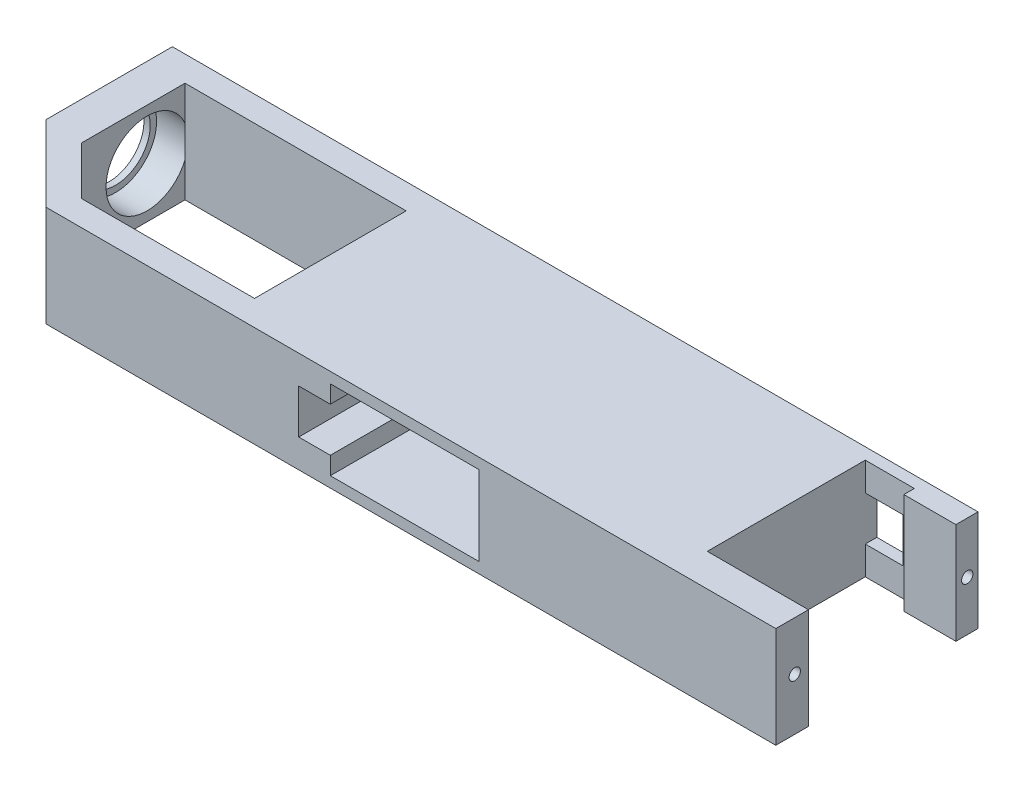
SolidWorks part; units mm, degrees
ref_plane "Front Plane" through (0, 0, 0) normal (0, 0, 1) x (1, 0, 0)
ref_plane "Top Plane" through (0, 0, 0) normal (0, 1, 0) x (1, 0, 0)
ref_plane "Right Plane" through (0, 0, 0) normal (1, 0, 0) x (0, 0, -1)
ref_axis "Axis1" through (0, 0, -88.99) along (0, 0, 1)
ref_axis "Axis2" through (88.99, 0, 0) along (-1, 0, 0)
sketch "Sketch1" plane through (0, 0, 0) normal (0, 1, 0) x (1, 0, 0)
  line L0 (64, -16.836) -> (47.9935, -16.836)
  line L1 (-63.5, 10) -> (64, 10)
  line L2 (-63.5, 10) -> (-63.5, -10)
  line L3 (-51.5, -22) -> (64, -22)
  line L4 (64, 10) -> (64, 6.5)
  line L5 (47.9935, -16.836) -> (47.9935, 8.164)
  line L6 (-63.5, -10) -> (-51.5, -22)
  line L8 (47.9935, 8.164) -> (55.7639, 8.164)
  line L9 (55.7639, 8.164) -> (55.7639, 6.5)
  line L10 (55.7639, 6.5) -> (64, 6.5)
  line L11 (64, -16.836) -> (64, -22)
  point P2 (-63.5, 0)
  dimension "D1" = 127.5
  dimension "D2" = 32
  dimension "D3" = 20
  dimension "D4" = 63.5
  dimension "D5" = 45
  dimension "D6" = 5.164
  dimension "D7" = 16.0065
  dimension "D8" = 25
  dimension "D9" = 3.5
  dimension "D10" = 8.2361
extrude "Boss-Extrude1" add sketch "Sketch1" along normal blind 8 and the other way blind 8
sketch "Sketch2" plane through (-63.5, 0, 0) normal (-1, 0, 0) x (0, 0, 1)
  circle A0 centre (0, 0) radius 5.5
  dimension "D1" = 11
extrude "Cut-Extrude1" cut sketch "Sketch2" against normal blind 8
sketch "Sketch3" plane through (0, 8, 0) normal (0, 1, 0) x (1, 0, 0)
  line L7 (-57.5, 6) -> (-22.5, 6)
  line L8 (-22.5, 6) -> (-22.5, -18)
  line L9 (-22.5, -18) -> (-49.8431, -18)
  line L10 (-49.8431, -18) -> (-57.5, -10.3431)
  line L11 (-57.5, -10.3431) -> (-57.5, 6)
  line L12 (-63.5, 10) -> (-63.5, -10) construction
  line L13 (-63.5, -10) -> (-51.5, -22) construction
  line L14 (64, 10) -> (-63.5, 10) construction
  line L15 (-51.5, -22) -> (64, -22) construction
  dimension "D1" = 6
  dimension "D2" = 4
  dimension "D3" = 4
  dimension "D4" = 4
  dimension "D5" = 35
extrude "Cut-Extrude2" cut sketch "Sketch3" against normal blind 16
sketch "Sketch4" plane through (-57.5, 0, 0) normal (1, 0, 0) x (0, 0, -1)
  circle A0 centre (0, 0) radius 6.5
  dimension "D1" = 13
extrude "Cut-Extrude3" cut sketch "Sketch4" against normal offset from surface (5 mm away) 1 contours A0 up to face at (-63.5, 0, 5.5)
sketch "Sketch5" plane through (0, 0, -10) normal (0, 0, -1) x (-1, 0, 0)
  line L0 (-64, 8) -> (63.5, 8) construction
  line L1 (-17, 6.3) -> (6.5, 6.3)
  line L2 (-17, 6.3) -> (-17, -6.3)
  line L3 (-17, -6.3) -> (6.5, -6.3)
  line L4 (6.5, 6.3) -> (6.5, -6.3)
  line L5 (-64, -8) -> (63.5, -8) construction
  line L6 (63.5, -8) -> (63.5, 8) construction
  dimension "D1" = 1.7
  dimension "D2" = 1.7
  dimension "D3" = 57
  dimension "D4" = 23.5
extrude "Cut-Extrude4" cut sketch "Sketch5" against normal through all
sketch "Sketch6" plane through (0, 0, -10) normal (0, 0, -1) x (-1, 0, 0)
  circle A0 centre (8.3, 0) radius 0.9
  circle A1 centre (-19, 0) radius 0.9
  dimension "D1" = 1.8
  dimension "D2" = 1.8
extrude "Cut-Extrude5" cut sketch "Sketch6" against normal blind 7
sketch "Sketch7" plane through (0, 0, -10) normal (0, 0, -1) x (-1, 0, 0)
  line L0 (-64, -8) -> (63.5, -8) construction
  line L1 (-47.9935, 3.5) -> (-53.9935, 3.5)
  line L2 (-47.9935, 3.5) -> (-47.9935, -3.5)
  line L3 (-47.9935, -3.5) -> (-53.9935, -3.5)
  line L4 (-53.9935, 3.5) -> (-53.9935, -3.5)
  point P4 (-47.9935, 0)
  dimension "D1" = 7
  dimension "D2" = 6
  dimension "D3" = 8
  dimension "D4" = 0
extrude "Cut-Extrude6" cut sketch "Sketch7" against normal blind 7
sketch "Sketch8" plane through (0, 0, 22) normal (0, 0, 1) x (1, 0, 0)
  line L0 (-6.5, -6.3) -> (-6.5, 6.3) construction
  line L1 (-6.5, -3.5) -> (-11.5, -3.5)
  line L2 (-6.5, -3.5) -> (-6.5, 3.5)
  line L3 (-6.5, 3.5) -> (-11.5, 3.5)
  line L4 (-11.5, -3.5) -> (-11.5, 3.5)
  point P6 (-6.5, -1.2467)
  point P7 (-6.5, 0)
  point P8 (-6.5, 0)
  dimension "D1" = 5
  dimension "D2" = 7
extrude "Cut-Extrude7" cut sketch "Sketch8" against normal blind 23
sketch "Sketch9" plane through (64, 0, 0) normal (1, 0, 0) x (0, 0, -1)
  circle A0 centre (-18.9984, 0.247) radius 0.9
  circle A1 centre (8.2993, -0.1079) radius 0.9
  dimension "D1" = 1.8
  dimension "D2" = 1.8
extrude "Cut-Extrude8" cut sketch "Sketch9" against normal blind 7
